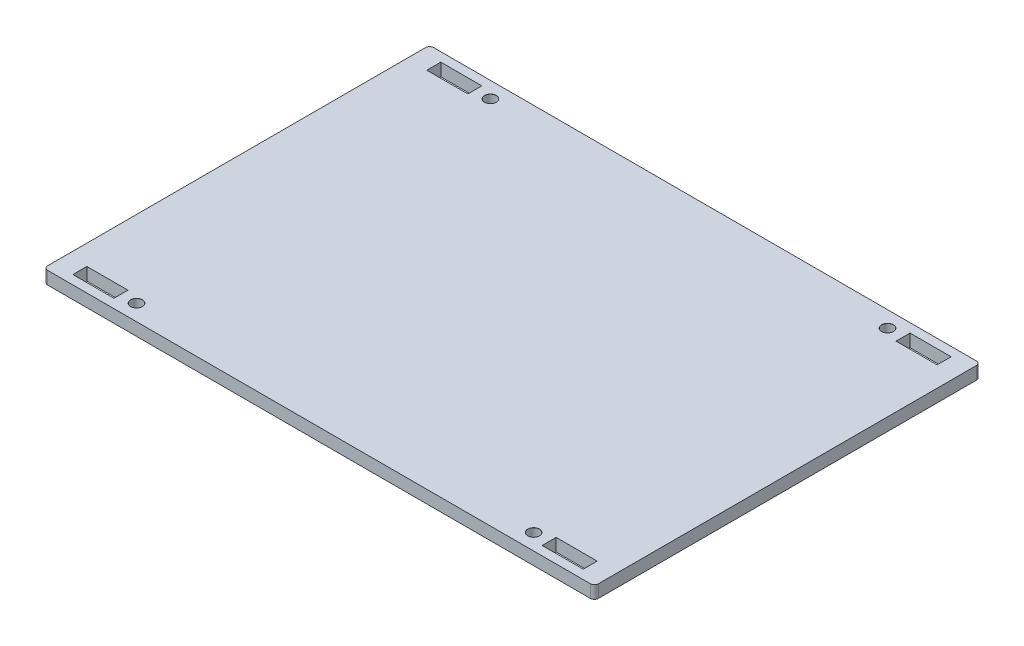
SolidWorks part; units mm, degrees
material "MDF"
ref_plane "Front Plane" through (0, 0, 0) normal (0, 0, 1) x (1, 0, 0)
ref_plane "Top Plane" through (0, 0, 0) normal (0, 1, 0) x (1, 0, 0)
ref_plane "Right Plane" through (0, 0, 0) normal (1, 0, 0) x (0, 0, -1)
sketch "Sketch1" plane through (0, 0, 0) normal (0, 1, 0) x (1, 0, 0)
  line L1 (-68.745, -48.1725) -> (68.745, -48.1725)
  line L2 (-68.745, -48.1725) -> (-68.745, 48.1725)
  line L3 (-68.745, 48.1725) -> (68.745, 48.1725)
  line L4 (68.745, -48.1725) -> (68.745, 48.1725)
  line L5 (-68.745, -48.1725) -> (68.745, 48.1725) construction
  line L6 (-68.745, 48.1725) -> (68.745, -48.1725) construction
  line L7 (-68.745, -44.1725) -> (68.745, -44.1725) construction
  line L8 (-68.745, -44.1725) -> (-68.745, 44.1725)
  line L9 (-68.745, 44.1725) -> (68.745, 44.1725) construction
  line L10 (68.745, -44.1725) -> (68.745, 44.1725)
  line L11 (-68.745, -44.1725) -> (68.745, 44.1725) construction
  line L12 (-68.745, 44.1725) -> (68.745, -44.1725) construction
  line L13 (-63.695, 42.4262) -> (-53.445, 42.4262)
  line L14 (-63.695, 42.4262) -> (-63.695, 45.9187)
  line L15 (-63.695, 45.9187) -> (-53.445, 45.9187)
  line L16 (-53.445, 42.4262) -> (-53.445, 45.9187)
  line L17 (-63.695, 42.4262) -> (-53.445, 45.9187) construction
  line L18 (-63.695, 45.9187) -> (-53.445, 42.4262) construction
  circle A0 centre (-49.57, 44.1725) radius 2.5
  point P0 (0, 0)
  point P6 (0, 0)
  point P11 (-58.57, 44.1725)
  dimension "D8" = 5
  dimension "D1" = 88.345
  dimension "D2" = 137.49
  dimension "D3" = 4
  dimension "D4" = 10.175
  dimension "D5" = 10.25
  dimension "D6" = 3.4925
  dimension "D7" = 19.175
extrude "Boss-Extrude1" add sketch "Sketch1" along normal blind 3.175 contours L1 L4 L3 L2 A0 L16 L13 L14 L15 | L13 L16 L15 L14 | A0 region at (0.2327, 0, 0.1856) region at (-58.57, 0, -44.1725) region at (-49.57, 0, -44.1725)
extrude "Cut-Extrude1" cut sketch "Sketch1<3>" against normal through all both and the other way through all contours L13 L16 L15 L14 region at (-58.57, 0, -44.1725)
sketch "Sketch1<3>" plane through (0, 0, 0) normal (0, 1, 0) x (1, 0, 0) same geometry as "Sketch1"
hole_wizard "M2.5 Clearance Hole1" positions "Sketch2" profile "Sketch3" hole size "M2.5" standard "ANSI Metric" end condition through all
sketch "Sketch2" plane through (0, 3.175, 0) normal (0, 1, 0) x (1, 0, 0)
  point P0 (-49.57, 44.1725)
sketch "Sketch3" plane through (-49.57, 3.175, -44.1725) normal (1, 0, 0) x (0, 0, 1)
  line L0 (0, 0) -> (0, 3.175)
  line L1 (0, 3.175) -> (1.45, 3.175)
  line L2 (1.45, 3.175) -> (1.45, 0.021)
  line L3 (1.45, 0.021) -> (1.475, 0)
  line L5 (1.475, 0) -> (0, 0)
  line L6 (-1.45, 0.021) -> (-1.475, 0) construction
  line L11 (0, -6.35) -> (0, 107.95) construction
  dimension "Thru Hole Dia." = 2.9
  dimension "Thru Hole Depth" = 3.175
  dimension "Near C'Sink Dia." = 2.95
  dimension "Near C'Sink Angle" = 100
mirror "Mirror1" about plane through (0, 0, 0) normal (1, 0, 0) of "M2.5 Clearance Hole1", "Cut-Extrude1" second plane through (0, 0, 0) second plane normal (0, 0, 1)
fillet "Fillet1" radius 1 4 edges at (68.745, 1.5875, -48.1725) (68.745, 1.5875, 48.1725) (-68.745, 1.5875, 48.1725) (-68.745, 1.5875, -48.1725)
